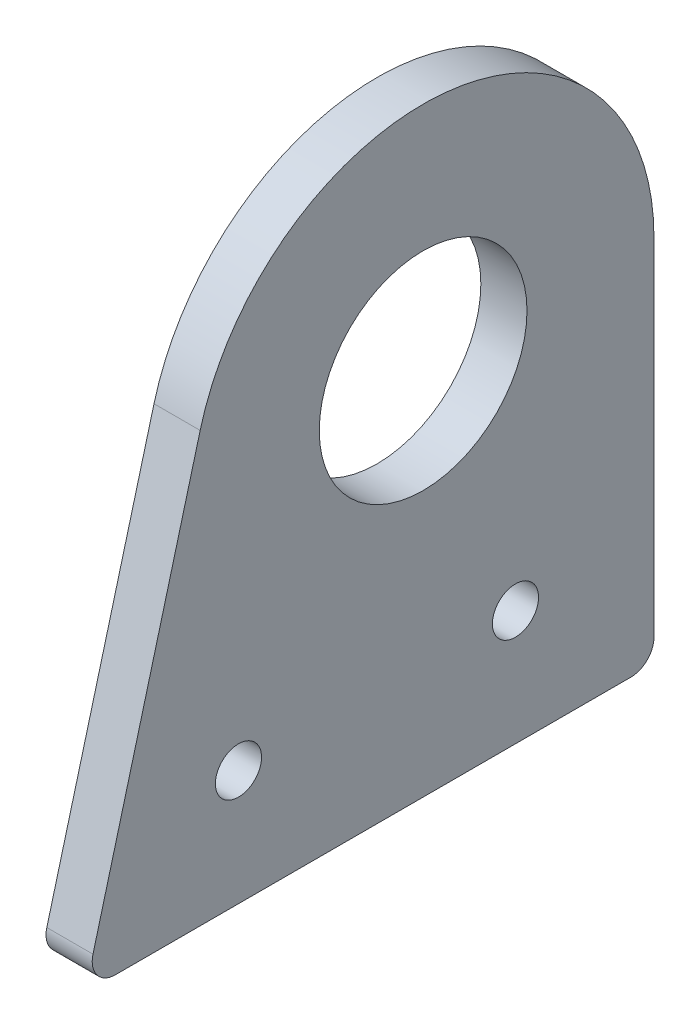
SolidWorks part; units mm, degrees
ref_plane "Front Plane" through (0, 0, 0) normal (0, 0, 1) x (1, 0, 0)
ref_plane "Top Plane" through (0, 0, 0) normal (0, 1, 0) x (1, 0, 0)
ref_plane "Right Plane" through (0, 0, 0) normal (1, 0, 0) x (0, 0, -1)
sketch "Sketch2" plane through (0, 0, 0) normal (1, 0, 0) x (0, 0, -1)
  line L0 (-168.275, 19.05) -> (-64.7217, 19.05) construction
  line L1 (-4.292, -28.2508) -> (89.7471, -42.5375) construction
  line L2 (-171.45, 22.225) -> (-171.45, 41.275) construction
  line L3 (-168.275, 44.45) -> (-101.6, 44.45) construction
  line L4 (-30.6681, 154.2675) -> (-45.2207, 99.9565)
  line L5 (41.6129, 175.1877) -> (218.62, -77.6046) construction
  line L6 (15.0515, 157.8062) -> (118.3631, 25.535) construction
  line L7 (53.6439, -14.125) -> (-17.3081, 137.9762) construction
  line L8 (-4.6354, 18.5275) -> (78.6163, 39.3564) construction
  line L9 (80.5683, -35.188) -> (-3.6594, -18.7447) construction
  line L10 (96.725, 25.2801) -> (96.9473, 25.8909) construction
  line L11 (55, 0) -> (-55, 0) construction
  line L12 (-20.2056, -20.2056) -> (-55.7414, 15.3303) construction
  line L13 (0, 95.25) -> (255.6229, 95.25) construction
  line L14 (0, 50.8) -> (255.6229, 50.8) construction
  line L15 (122.3804, 3.2387) -> (110.5619, -30.0732) construction
  line L16 (31.75, 146.05) -> (31.75, 110.6081)
  line L17 (94.5769, 26.062) -> (94.7992, 26.6728) construction
  line L18 (98.8732, 24.4983) -> (99.0955, 25.1091) construction
  line L19 (68.3924, -14.8897) -> (67.8097, -15.722) construction
  line L21 (66.5198, -13.5785) -> (65.9371, -14.4108) construction
  line L22 (92.6084, -23.7036) -> (92.5198, -24.7158) construction
  line L23 (94.8857, -23.9029) -> (94.7971, -24.915) construction
  line L26 (96.9473, 25.8909) -> (68.3924, -14.8897) construction
  line L27 (96.9473, 25.8909) -> (92.6084, -23.7036) construction
  line L28 (88.26, 2.0227) -> (96.9473, 25.8909) construction
  line L29 (-95.25, 50.8) -> (-95.25, 83.8035) construction
  line L30 (-69.8795, 95.25) -> (-51.3544, 95.25) construction
  line L31 (-71.523, 95.0336) -> (-90.5435, 89.9371) construction
  line L32 (0, 0) -> (87.8872, 2.3014) construction
  line L33 (0, 146.05) -> (88.26, 2.0227) construction
  line L34 (31.75, 110.6081) -> (31.75, 98.425)
  line L35 (33.6435, 106.0845) -> (117.7963, 23.1789) construction
  line L36 (-45.2207, 99.9565) -> (-45.4109, 99.2468)
  line L37 (-42.3441, 95.25) -> (28.575, 95.25)
  line L38 (0, 55) -> (0, -55) construction
  circle A0 centre (0, 146.05) radius 14.2875
  circle A1 centre (0, 0) radius 14.2875 construction
  circle A2 centre (0, 146.05) radius 50.8 construction
  circle A3 centre (0, 0) radius 50.8 construction
  circle A5 centre (-57.15, 31.75) radius 3.556 construction
  circle A6 centre (-82.55, 31.75) radius 3.556 construction
  circle A7 centre (-107.95, 31.75) radius 3.556 construction
  circle A8 centre (-133.35, 31.75) radius 3.556 construction
  circle A9 centre (-158.75, 31.75) radius 3.556 construction
  arc A10 (31.75, 146.05) -> (-30.6681, 154.2675) centre (0, 146.05) ccw
  arc A11 (-171.45, 41.275) -> (-168.275, 44.45) centre (-168.275, 41.275) cw construction
  arc A12 (-168.275, 19.05) -> (-171.45, 22.225) centre (-168.275, 22.225) cw construction
  arc A14 (-55.7414, 15.3303) -> (-64.7217, 19.05) centre (-64.7217, 6.35) ccw construction
  arc A15 (-4.6354, 18.5275) -> (-3.6594, -18.7447) centre (0, 0) ccw construction
  arc A16 (15.0515, 157.8062) -> (-17.3081, 137.9762) centre (0, 146.05) ccw construction
  arc A17 (53.6439, -14.125) -> (118.3631, 25.535) centre (88.26, 2.0227) ccw construction
  arc A18 (80.5683, -35.188) -> (78.6163, 39.3564) centre (87.8872, 2.3014) ccw construction
  circle A19 centre (87.8872, 2.3014) radius 32 construction
  circle A20 centre (88.26, 2.0227) radius 32 construction
  circle A21 centre (88.26, 2.0227) radius 24.75 construction
  circle A24 centre (87.8872, 2.3014) radius 24.75 construction
  arc A29 (-20.2056, -20.2056) -> (-4.292, -28.2508) centre (0, 0) ccw construction
  arc A30 (122.3804, 3.2387) -> (117.7963, 23.1789) centre (104.4268, 9.6083) ccw construction
  arc A31 (89.7471, -42.5375) -> (110.5619, -30.0732) centre (92.6084, -23.7036) ccw construction
  circle A32 centre (88.26, 2.0227) radius 14.2875 construction
  circle A33 centre (87.8872, 2.3014) radius 14.2875 construction
  arc A34 (94.5769, 26.062) -> (98.8732, 24.4983) centre (96.725, 25.2801) ccw construction
  arc A35 (99.0955, 25.1091) -> (94.7992, 26.6728) centre (96.9473, 25.8909) ccw construction
  arc A37 (65.9371, -14.4108) -> (66.4985, -17.5946) centre (67.8097, -15.722) ccw construction
  arc A38 (94.8857, -23.9029) -> (92.8076, -21.4263) centre (92.6084, -23.7036) ccw construction
  arc A39 (92.3206, -26.9931) -> (94.7971, -24.915) centre (92.5198, -24.7158) ccw construction
  arc A40 (69.7036, -13.0172) -> (92.8076, -21.4263) centre (96.9473, 25.8909) ccw construction
  arc A41 (66.4985, -17.5946) -> (92.3206, -26.9931) centre (96.9473, 25.8909) ccw construction
  arc A42 (69.7036, -13.0172) -> (66.5198, -13.5785) centre (68.3924, -14.8897) ccw construction
  circle A43 centre (-82.55, 57.15) radius 3.556 construction
  circle A44 centre (-82.55, 82.55) radius 3.556 construction
  arc A45 (-51.3544, 95.25) -> (-45.2207, 99.9565) centre (-51.3544, 101.6) ccw construction
  arc A46 (-95.25, 50.8) -> (-101.6, 44.45) centre (-101.6, 50.8) cw construction
  arc A48 (-90.5435, 89.9371) -> (-95.25, 83.8035) centre (-88.9, 83.8035) ccw construction
  arc A49 (-71.523, 95.0336) -> (-69.8795, 95.25) centre (-69.8795, 88.9) cw construction
  arc A50 (33.6435, 106.0845) -> (31.75, 110.6081) centre (38.1, 110.6081) cw construction
  arc A51 (28.575, 95.25) -> (31.75, 98.425) centre (28.575, 98.425) ccw
  arc A52 (-45.4109, 99.2468) -> (-42.3441, 95.25) centre (-42.3441, 98.425) ccw
  circle A53 centre (-25.4, 111.125) radius 3.175
  circle A54 centre (12.7, 111.125) radius 3.175
  point P50 (96.8362, 25.5855)
  point P76 (-95.25, 88.676)
  point P79 (102.7469, -16.3909)
  point P97 (-70.7155, 95.25)
  point P105 (31.75, 95.25)
  point P113 (31.75, 107.95)
  point P116 (-24.8024, 117.8467)
  dimension "D1" = 28.575
  dimension "D2" = 101.6
  dimension "D3" = 44.45
  dimension "D4" = 19.05
  dimension "D6" = 57.15
  dimension "D8" = 7.112
  dimension "D14" = 105
  dimension "D15" = 3.175
  dimension "D16" = 12.7
  dimension "D18" = 38.1972
  dimension "D19" = 76.3944
  dimension "D20" = 520
  dimension "D21" = 360
  dimension "D22" = 64
  dimension "D23" = 49.5
  dimension "D24" = 4.572
  dimension "D25" = 19.05
  dimension "D26" = 31.75
  dimension "D27" = 25.4
  dimension "D28" = 2.286
  dimension "D29" = 1.016
  dimension "D36" = 25.4
  dimension "D38" = 12.7
  dimension "D39" = 6.35
  dimension "D40" = 15
  dimension "D42" = 6.35
  dimension "D43" = 5.588
  dimension "D44" = 58.5
  dimension "D47" = 31.75
  dimension "D48" = 12.7
  dimension "D50" = 6.35
  dimension "D51" = 3.175
  dimension "D52" = 38.1
  dimension "D55" = 6.35
  dimension "D5" = 135
  dimension "D7" = 12.7
  dimension "D9" = 57.15
  dimension "D10" = 12.7
  dimension "D12" = 25.4
  dimension "D13" = 12.7
  dimension "D17" = 55
  dimension "D30" = 3
  dimension "D31" = 30
  dimension "D32" = 15
  dimension "D33" = 50.8
  dimension "D34" = 50.8
  dimension "D35" = 1.016
  dimension "D37" = 12.7
  dimension "D41" = 25.4
  dimension "D45" = 1.5
  dimension "D46" = 110
  dimension "D49" = 12.7
  dimension "D53" = 12.7
  dimension "D54" = 15.875
  dimension "D11" = 5
extrude "Boss-Extrude1" add sketch "Sketch2" along normal blind 6.35
